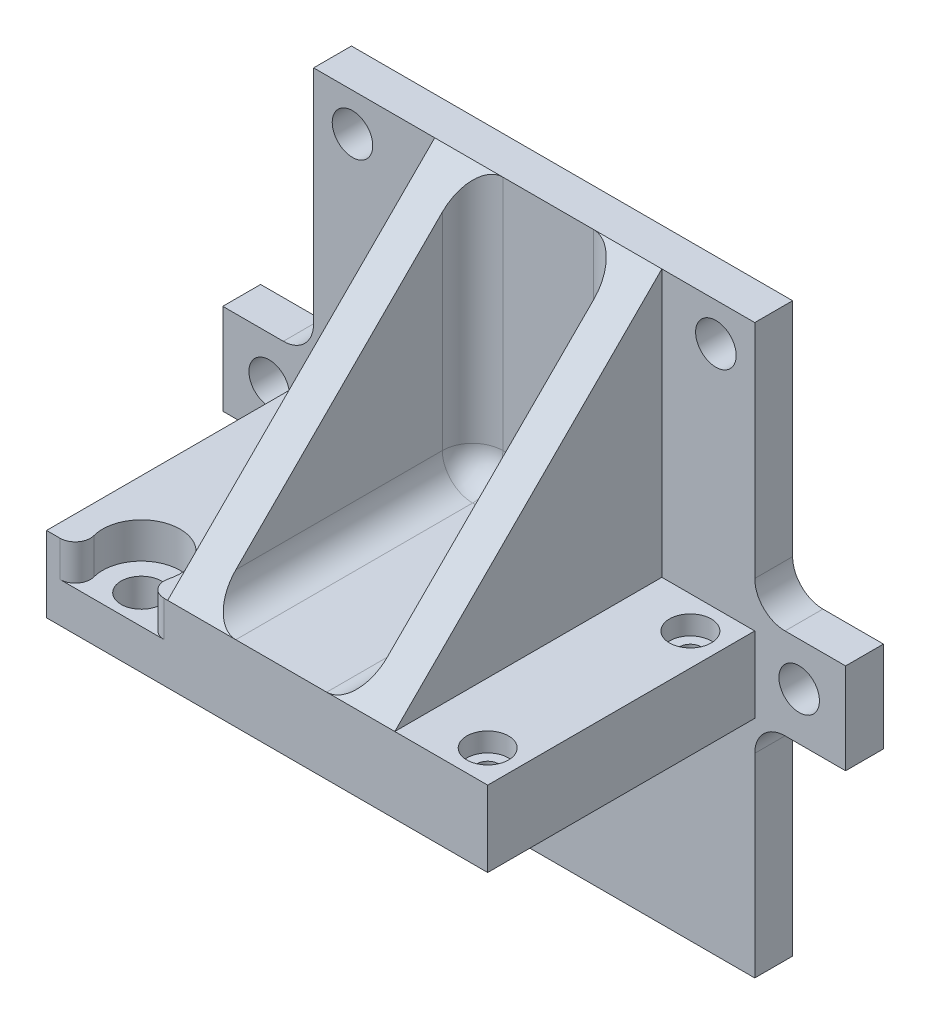
SolidWorks part; units mm, degrees
ref_plane "Front Plane" through (0, 0, 0) normal (0, 0, 1) x (1, 0, 0)
ref_plane "Top Plane" through (0, 0, 0) normal (0, 1, 0) x (1, 0, 0)
ref_plane "Right Plane" through (0, 0, 0) normal (1, 0, 0) x (0, 0, -1)
sketch "Sketch1" plane through (0, 0, 0) normal (0, 1, 0) x (1, 0, 0)
  line L0 (5.5, 2.45) -> (5.5, 0) construction
  line L1 (0, 0) -> (37, 0)
  line L2 (0, 0) -> (0, 22.4)
  line L3 (0, 22.4) -> (37, 22.4)
  line L4 (37, 0) -> (37, 22.4)
  line L5 (5.5, 19.95) -> (5.5, 22.4) construction
  line L6 (34.3, 19.7) -> (34.3, 22.4) construction
  line L7 (34.3, 2.7) -> (34.3, 0) construction
  point P5 (5.5, 19.95)
  point P6 (5.5, 2.45)
  point P7 (34.3, 19.7)
  point P8 (34.3, 2.7)
  dimension "D1" = 37
  dimension "D2" = 22.4
  dimension "D3" = 17.5
  dimension "D4" = 5.5
  dimension "D5" = 2.7
  dimension "D6" = 2.7
extrude "Boss-Extrude1" add sketch "Sketch1" along normal blind 6.35
sketch "Sketch7" plane through (37, 0, 0) normal (1, 0, 0) x (0, 0, -1)
  line L0 (0, -18.86) -> (0, 28.75)
  line L1 (0, 28.75) -> (-3.175, 28.75)
  line L2 (-3.175, 28.75) -> (-3.175, -18.86)
  line L3 (-3.175, -18.86) -> (0, -18.86)
  line L4 (0, 0) -> (22.4, 0) construction
  dimension "D1" = 3.175
  dimension "D2" = 18.86
  dimension "D3" = 22.4
extrude "Boss-Extrude2" add sketch "Sketch7" against normal up to surface (37 mm away) up to face at (0, 3.175, -11.2)
ref_plane "CBORE PLANE" through (0, 13.97, 0) normal (0, 1, 0) x (1, 0, 0)
hole_wizard "CBORE for M3 SHCS3" positions "Sketch12" profile "Sketch13" counterbore size "M3" standard "ANSI Metric" end condition through all
sketch "Sketch12" plane through (0, 13.97, 0) normal (0, 1, 0) x (1, 0, 0)
  point P0 (5.5, 2.45)
  point P3 (5.5, 19.95)
sketch "Sketch13" plane through (5.5, 13.97, -2.45) normal (1, 0, 0) x (0, 0, 1)
  line L0 (0, 0) -> (0, 32.83)
  line L1 (0, 32.83) -> (1.7, 32.83)
  line L3 (1.7, 32.83) -> (1.7, 10.62)
  line L4 (1.7, 10.62) -> (3.25, 10.62)
  line L5 (3.25, 10.62) -> (3.25, 0)
  line L7 (3.25, 0) -> (0, 0)
  line L11 (0, -6.35) -> (0, 107.95) construction
  dimension "Thru Hole Dia." = 3.4
  dimension "Thru Hole Depth" = 32.83
  dimension "C'Bore Dia." = 6.5
  dimension "C'Bore Depth" = 10.62
hole_wizard "CBORE for M1.6 SHCS1" positions "Sketch14" profile "Sketch15" counterbore size "M1.6" standard "ANSI Metric" end condition through all
sketch "Sketch14" plane through (0, 6.35, 0) normal (0, 1, 0) x (1, 0, 0)
  point P0 (34.3, 19.7)
  point P3 (34.3, 2.7)
sketch "Sketch15" plane through (34.3, 6.35, -19.7) normal (1, 0, 0) x (0, 0, 1)
  line L0 (0, 0) -> (0, 25.21)
  line L1 (0, 25.21) -> (0.9, 25.21)
  line L3 (0.9, 25.21) -> (0.9, 1.6)
  line L4 (0.9, 1.6) -> (1.75, 1.6)
  line L5 (1.75, 1.6) -> (1.75, 0)
  line L7 (1.75, 0) -> (0, 0)
  line L11 (0, -6.35) -> (0, 107.95) construction
  dimension "Thru Hole Dia." = 1.8
  dimension "Thru Hole Depth" = 25.21
  dimension "C'Bore Dia." = 3.5
  dimension "C'Bore Depth" = 1.6
sketch "Sketch16" plane through (0, 0, 0) normal (-1, 0, 0) x (0, 0, 1)
  line L0 (-22.4, 6.35) -> (0, 6.35)
  line L1 (0, 6.35) -> (0, 28.75)
  line L2 (0, 28.75) -> (-22.4, 6.35)
extrude "Boss-Extrude3" add sketch "Sketch16" against normal blind 3.175 from offset 10.16 offset against normal yes
extrude "Boss-Extrude4" add sketch "Sketch16<2>" along normal blind 3.175 from offset 29.21 offset against normal yes
sketch "Sketch16<2>" plane through (0, 0, 0) normal (-1, 0, 0) x (0, 0, 1) same geometry as "Sketch16"
sketch "Sketch18" plane through (0, 0, 0) normal (0, 0, 1) x (1, 0, 0)
  line L9 (37, 0) -> (44.62, 0)
  line L10 (37, 0) -> (37, 7.62)
  line L11 (37, 7.62) -> (44.62, 7.62)
  line L12 (44.62, 0) -> (44.62, 7.62)
  line L13 (0, 0) -> (-7.62, 0)
  line L14 (0, 0) -> (0, 7.62)
  line L15 (0, 7.62) -> (-7.62, 7.62)
  line L16 (-7.62, 0) -> (-7.62, 7.62)
  dimension "D1" = 7.62
  dimension "D2" = 7.62
extrude "Boss-Extrude5" add sketch "Sketch18" along normal through all
sketch "Mounting Hole Locations" plane through (0, 0, 0) normal (0, 0, -1) x (-1, 0, 0)
  line L0 (-18.5, -18.86) -> (-18.5, 28.75) construction
  line L1 (0, -18.86) -> (-37, -18.86) construction
  line L2 (-13.335, 28.75) -> (-26.035, 28.75) construction
  line L3 (-29.21, 28.75) -> (-37, 28.75) construction
  point P2 (-33.74, 25.575)
  point P13 (-40.725, 3.985)
  point P16 (-3.26, 25.575)
  point P17 (3.725, 3.985)
  dimension "D1" = 21.59
  dimension "D2" = 15.24
  dimension "D3" = 3.175
  dimension "D4" = 22.225
hole_wizard "M3 Clearance Hole1" positions "Sketch19" profile "Sketch20" hole size "M3" standard "ANSI Metric" end condition through all
sketch "Sketch19" plane through (0, 0, 0) normal (0, 0, -1) x (-1, 0, 0)
  point P0 (-40.725, 3.985)
  point P3 (-33.74, 25.575)
  point P6 (-3.26, 25.575)
  point P9 (3.725, 3.985)
sketch "Sketch20" plane through (40.725, 3.985, 0) normal (1, 0, 0) x (0, 1, 0)
  line L0 (0, 0) -> (0, 3.175)
  line L1 (0, 3.175) -> (1.7, 3.175)
  line L2 (1.7, 3.175) -> (1.7, 0)
  line L5 (1.7, 0) -> (0, 0)
  line L11 (0, -6.35) -> (0, 107.95) construction
  dimension "Thru Hole Dia." = 3.4
  dimension "Thru Hole Depth" = 3.175
fillet "Fillet1" radius 2.54 9 edges at (13.335, 6.35, -11.2) (13.335, 17.55, 0) (26.035, 6.35, -11.2) (26.035, 17.55, 0) (19.685, 6.35, 0) (0, 7.62, 1.5875) (0, 0, 1.5875) (37, 0, 1.5875) (37, 7.62, 1.5875)
fillet "Fillet2" radius 1.27 2 edges at (3.3646, 4.85, -22.4) (7.6354, 4.85, -22.4)
mirror "Mirror1" about plane through (0, 0, 0) normal (0, 0, 1) of bodies 112
delete or keep bodies "Body-Delete/Keep 1" type delete bodies bodies 112
